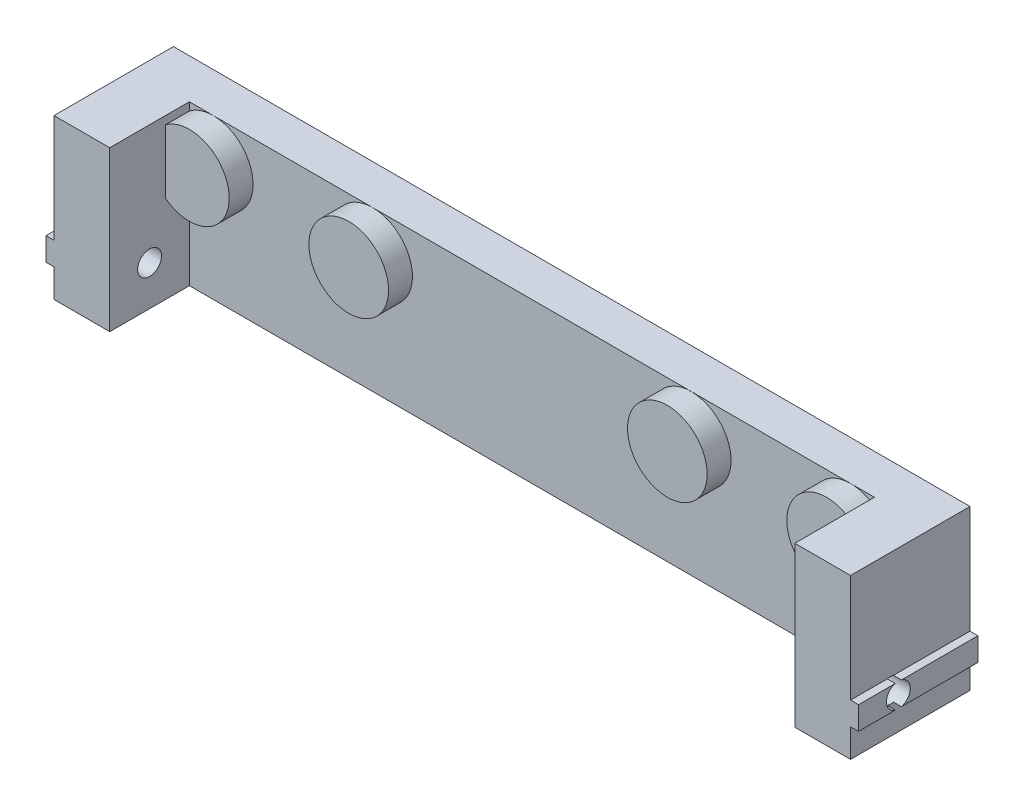
SolidWorks part; units mm, degrees
ref_plane "Front Plane" through (0, 0, 0) normal (0, 0, 1) x (1, 0, 0)
ref_plane "Top Plane" through (0, 0, 0) normal (0, 1, 0) x (1, 0, 0)
ref_plane "Right Plane" through (0, 0, 0) normal (1, 0, 0) x (0, 0, -1)
sketch "Sketch1" plane through (0, 0, 0) normal (0, 0, 1) x (1, 0, 0)
  line L0 (-50, 0) -> (50, 0)
  line L1 (-50, 0) -> (-50, 3.55)
  line L2 (-50, 3.55) -> (-51, 3.55)
  line L3 (-51, 3.55) -> (-51, 6.45)
  line L4 (-51, 6.45) -> (-50, 6.45)
  line L7 (-50, 6.45) -> (-50, 20)
  line L8 (-50, 20) -> (50, 20)
  line L9 (50, 20) -> (50, 6.45)
  line L12 (50, 6.45) -> (51, 6.45)
  line L13 (51, 6.45) -> (51, 3.55)
  line L14 (51, 3.55) -> (50, 3.55)
  line L15 (50, 3.55) -> (50, 0)
  point P8 (50.5, 6.45)
  point P9 (-52.4291, 3.55)
  point P10 (-50, 6.1331)
  point P17 (0, 0)
  point P18 (51, 6.4204)
  point P19 (28.9436, 18.0456)
  point P20 (-42.5757, 10)
  point P21 (42.7548, 10)
  point P24 (0, 0)
  dimension "D1" = 100
  dimension "D2" = 3.55
  dimension "D3" = 2.9
  dimension "D4" = 1
  dimension "D5" = 20
extrude "Main" add sketch "Sketch1" along normal blind 15
sketch "Sketch2" plane through (0, 0, 15) normal (0, 0, 1) x (1, 0, 0)
  line L0 (-50, 0) -> (50, 0) construction
  line L1 (-43, 0) -> (43, 0)
  line L2 (-43, 0) -> (-43, 20)
  line L3 (-43, 20) -> (43, 20)
  line L4 (43, 0) -> (43, 20)
  line L5 (-50, 3.55) -> (-50, 0) construction
  line L6 (50, 0) -> (50, 3.55) construction
  line L7 (50, 20) -> (-50, 20) construction
  point P10 (50, 1.775)
  dimension "D1" = 7
  dimension "D2" = 7
extrude "TopExtrusion" cut sketch "Sketch2" against normal blind 10
sketch "Sketch5" plane through (0, 0, 5) normal (0, 0, 1) x (1, 0, 0)
  line L0 (-43, 0) -> (43, 0) construction
  circle A0 centre (-40, 15) radius 5
  circle A1 centre (-20, 15) radius 5
  circle A2 centre (20, 15) radius 5
  circle A3 centre (40, 15) radius 5
  point P11 (0, 0)
  dimension "D1" = 10
  dimension "D2" = 15
  dimension "D3" = 40
  dimension "D4" = 40
  dimension "D5" = 20
  dimension "D6" = 20
extrude "ReinforcementHoles" add sketch "Sketch5" along normal blind 3
sketch "Sketch3" plane through (0, 0, 0) normal (0, 0, 1) x (1, 0, 0)
  line L0 (-43, 0) -> (43, 0) construction
  circle A0 centre (-40, 15) radius 3
  circle A1 centre (20, 15) radius 3
  dimension "D1" = 6
  dimension "D4" = 60
  dimension "D2" = 15
  dimension "D3" = 40
extrude "Holes" cut sketch "Sketch3" along normal blind 5
mirror "Mirror1" about plane through (0, 0, 0) normal (1, 0, 0) of "Holes"
sketch "Sketch4" plane through (51, 0, 0) normal (1, 0, 0) x (0, 0, -1)
  line L0 (-15, 0) -> (0, 0) construction
  line L1 (-15, 3.55) -> (-15, 6.45) construction
  circle A0 centre (-10, 5) radius 1.5
  dimension "D1" = 5
  dimension "D3" = 3
  dimension "D2" = 5
extrude "FixHoles" cut sketch "Sketch4" against normal through all
